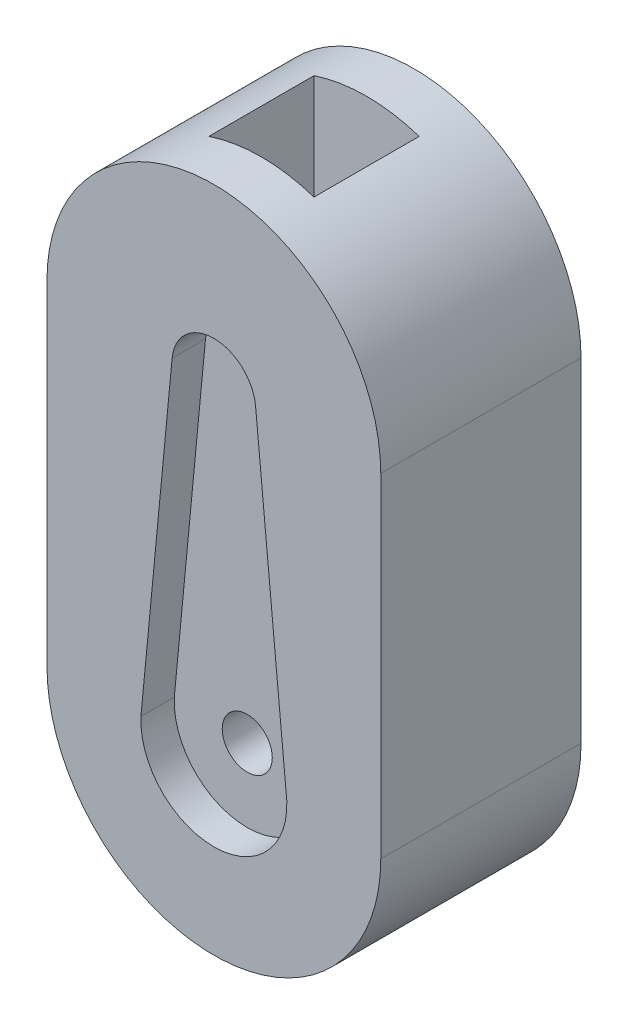
SolidWorks part; units mm, degrees
material "ABS"
ref_plane "Front Plane" through (0, 0, 0) normal (0, 0, 1) x (1, 0, 0)
ref_plane "Top Plane" through (0, 0, 0) normal (0, 1, 0) x (1, 0, 0)
ref_plane "Right Plane" through (0, 0, 0) normal (1, 0, 0) x (0, 0, -1)
sketch "Sketch1" plane through (0, 0, 0) normal (0, 0, 1) x (1, 0, 0)
  line L0 (0, 20) -> (0, 0) construction
  line L1 (10, 20) -> (10, 0)
  line L2 (-10, 20) -> (-10, 0)
  arc A1 (10, 20) -> (-10, 20) centre (0, 20) ccw
  arc A2 (-10, 0) -> (10, 0) centre (0, 0) ccw
  point P3 (0, 10)
  point P9 (0, 30)
  point P10 (0, -10)
  dimension "D1" = 20
  dimension "D2" = 40
sketch "Sketch2" plane through (0, 0, 0) normal (0, 0, 1) x (1, 0, 0)
  line L0 (0, 0) -> (0, 30) construction
  line L1 (-2.5, 19.7394) -> (-4.37, 0.2091)
  line L2 (2.5, 19.7394) -> (4.37, 0.2091)
  line L3 (-10, 0) -> (10, 0) construction
  line L8 (-10, 20) -> (-10, 0) construction
  line L9 (10, 20) -> (10, 0) construction
  arc A0 (-4.37, 0.2091) -> (4.37, -0.2091) centre (0, 0) ccw
  arc A2 (-2.5, 19.7394) -> (2.5, 19.7394) centre (0, 19.5) cw
  arc A3 (4.37, -0.2091) -> (4.37, 0.2091) centre (0, 0) ccw
  arc A5 (10, 20) -> (-10, 20) centre (0, 20) ccw construction
  dimension "D1" = 4.375
  dimension "D2" = 8.74
  dimension "D3" = 19.5
  dimension "D4" = 5
extrude "Boss-Extrude1" add sketch "Sketch1" against normal blind 12
sketch "Sketch4" plane through (0, 0, 0) normal (0, 0, 1) x (1, 0, 0)
  circle A0 centre (0, 0) radius 1.5
  dimension "D1" = 3
extrude "Cut-Extrude2" cut sketch "Sketch4" against normal through all
extrude "Cut-Extrude1" cut sketch "Sketch2" against normal blind 2
ref_plane "Plane1" through (0, 5, 0) normal (0, 1, 0) x (1, 0, 0)
sketch "Sketch6" plane through (0, 5, 0) normal (0, -1, 0) x (-1, 0, 0)
  line L0 (0, 12) -> (0, 0) construction
  line L13 (10, 12) -> (-10, 12) construction
  line L15 (-3.15, 9.15) -> (3.15, 9.15)
  line L17 (-3.15, 9.15) -> (-3.15, 2.85)
  line L18 (-3.15, 2.85) -> (3.15, 2.85)
  line L21 (3.15, 9.15) -> (3.15, 2.85)
  line L22 (-3.15, 9.15) -> (3.15, 2.85) construction
  line L23 (-3.15, 2.85) -> (3.15, 9.15) construction
  point P4 (0, 6)
  dimension "D1" = 6.3
extrude "Cut-Extrude3" cut sketch "Sketch6" against normal through all
ref_axis "Axis1" through (0, 0, -12) along (0, 0, 1)
